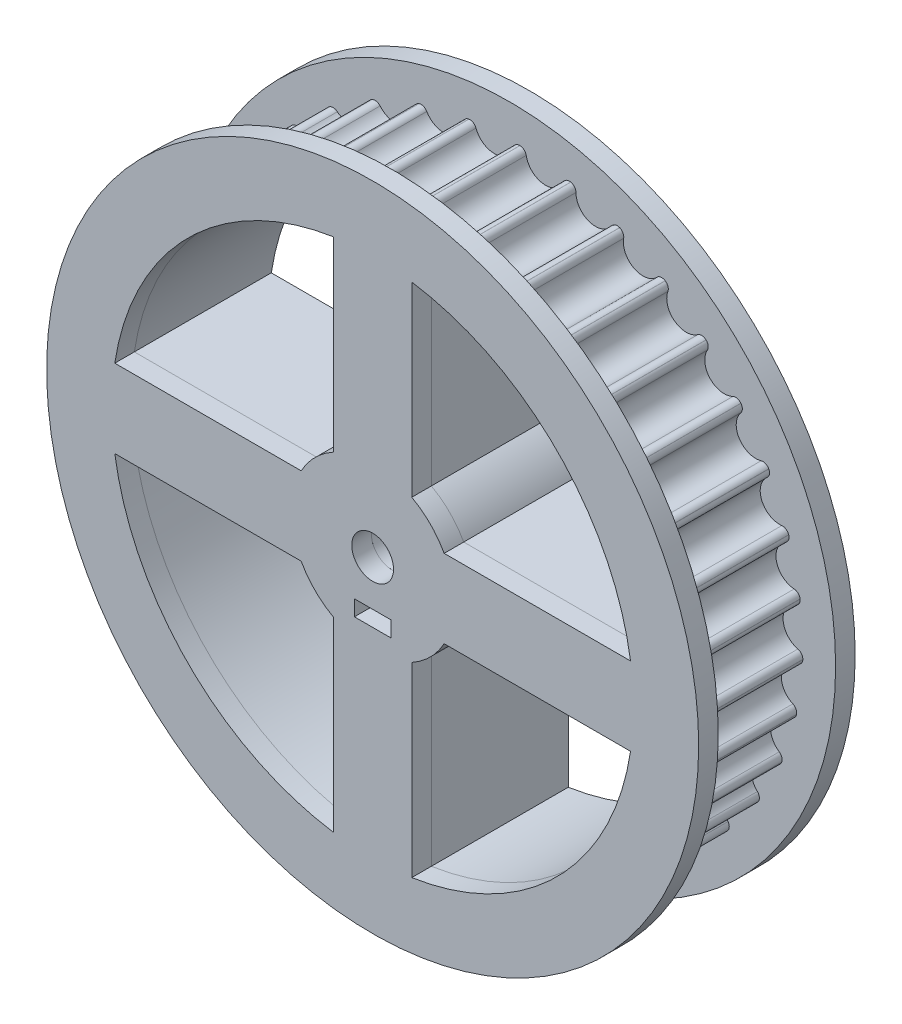
SolidWorks part; units mm, degrees
ref_plane "Front Plane" through (0, 0, 0) normal (0, 0, 1) x (1, 0, 0)
ref_plane "Top Plane" through (0, 0, 0) normal (0, 1, 0) x (1, 0, 0)
ref_plane "Right Plane" through (0, 0, 0) normal (1, 0, 0) x (0, 0, -1)
ref_plane "Plane1" through (0, 0, 18) normal (0, 0, 1) x (1, 0, 0)
sketch "Sketch1" plane through (0, 0, 0) normal (0, 0, 1) x (1, 0, 0)
  circle A0 centre (0, 0) radius 50
  circle A1 centre (0, 0) radius 45
  point P83 (0, 0)
  dimension "D1" = 100
  dimension "D2" = 90
extrude "Boss-Extrude1" add sketch "Sketch1" along normal blind 18 contours A1 region at (0, 0, 0)
sketch "Sketch3" plane through (0, 0, 0) normal (0, 0, 1) x (1, 0, 0)
  circle A0 centre (0, 0) radius 50
  dimension "D1" = 100
extrude "Boss-Extrude2" add sketch "Sketch3" against normal blind 3
sketch "Sketch10" plane through (0, 0, 18) normal (0, 0, 1) x (1, 0, 0)
  circle A0 centre (-44.6616, 5.5083) radius 3
  point P94 (0, 0)
  dimension "D1" = 6
extrude "Cut-Extrude7" cut sketch "Sketch10" against normal blind 18
fillet "Fillet1" radius 1 2 edges at (-44.1953, 8.4718, 9) (-44.9294, 2.5203, 9)
pattern_circular "CirPattern1" count 36 over 360 about axis through (0, 0, 18) along (0, 0, -1) of "Cut-Extrude7", "Fillet1" reverse direction yes
sketch "Sketch4" plane through (0, 0, 18) normal (0, 0, 1) x (1, 0, 0)
  line L0 (6, -39.5474) -> (6, -10.9659)
  line L1 (0, -11.55) -> (0, 11.55) construction
  line L2 (-6, -39.5474) -> (-6, -10.9659)
  line L3 (-39.5474, -6) -> (-10.9659, -6)
  line L4 (-39.5474, 6) -> (-10.9659, 6)
  line L5 (-6, 39.5474) -> (-6, 10.9659)
  line L6 (6, 39.5474) -> (6, 10.9659)
  line L7 (39.5474, 6) -> (10.9659, 6)
  line L8 (39.5474, -6) -> (10.9659, -6)
  arc A0 (6, -39.5474) -> (39.5474, -6) centre (0, 0) ccw
  arc A1 (-10.9659, -6) -> (-6, -10.9659) centre (0, 0) ccw
  arc A2 (-39.5474, -6) -> (-6, -39.5474) centre (0, 0) ccw
  arc A3 (10.9659, 6) -> (6, 10.9659) centre (0, 0) ccw
  arc A4 (39.5474, 6) -> (6, 39.5474) centre (0, 0) ccw
  arc A5 (-6, 39.5474) -> (-39.5474, 6) centre (0, 0) ccw
  arc A6 (-6, 10.9659) -> (-10.9659, 6) centre (0, 0) ccw
  arc A7 (6, -10.9659) -> (10.9659, -6) centre (0, 0) ccw
  circle A8 centre (0, 0) radius 3.2
  point P25 (0, 0)
  dimension "D1" = 25
  dimension "D2" = 80
  dimension "D5" = 6.4
  dimension "D3" = 6
  dimension "D4" = 4
extrude "Cut-Extrude1" cut sketch "Sketch4" against normal blind 22
sketch "Sketch5" plane through (0, 0, 18) normal (0, 0, 1) x (1, 0, 0)
  line L0 (-3, -39.6087) -> (3, -39.6087)
  line L1 (0, -11.55) -> (0, 11.55) construction
  line L2 (3, -39.6087) -> (3, -12.8861)
  line L3 (3, -12.8861) -> (-3, -12.8861)
  line L4 (-3, -39.6087) -> (-3, -12.8861)
  line L5 (-39.6087, 3) -> (-39.6087, -3)
  line L6 (-39.6087, -3) -> (-12.8861, -3)
  line L7 (-12.8861, -3) -> (-12.8861, 3)
  line L8 (-39.6087, 3) -> (-12.8861, 3)
  line L9 (3, 39.6087) -> (-3, 39.6087)
  line L10 (-3, 39.6087) -> (-3, 12.8861)
  line L11 (-3, 12.8861) -> (3, 12.8861)
  line L12 (3, 39.6087) -> (3, 12.8861)
  line L13 (39.6087, -3) -> (39.6087, 3)
  line L14 (39.6087, 3) -> (12.8861, 3)
  line L15 (12.8861, 3) -> (12.8861, -3)
  line L16 (39.6087, -3) -> (12.8861, -3)
  line L17 (-2.8, -9.314) -> (2.8, -9.314)
  line L18 (2.8, -9.314) -> (2.8, -6.914)
  line L19 (2.8, -6.914) -> (-2.8, -6.914)
  line L20 (-2.8, -9.314) -> (-2.8, -6.914)
  point P7 (0, -39.6087)
  point P8 (0, -12.8861)
  point P23 (0, 0)
  point P26 (0, -6.914)
  point P27 (0, -9.314)
  dimension "D1" = 3
  dimension "D3" = 5.6
  dimension "D4" = 2.4
  dimension "D2" = 4
extrude "Cut-Extrude2" cut sketch "Sketch5" against normal blind 25 contours L0 L2 L3 L4 | L13 L14 L15 L16 | L5 L6 L7 L8 | L9 L10 L11 L12 | L19 L20 L17 L18
sketch "Sketch6" plane through (0, 0, 0) normal (0, 1, 0) x (1, 0, 0)
  line L0 (50, 3) -> (-50, 3) construction
  line L1 (3.2, 3) -> (-3.2, 3) construction
  line L2 (0, -11.55) -> (0, 11.55) construction
  circle A0 centre (0, -4) radius 2
  circle A1 centre (0, -12) radius 2
  dimension "D3" = 4
  dimension "D1" = 7
  dimension "D2" = 15
extrude "Cut-Extrude3" cut sketch "Sketch6" along normal blind 1 and the other way blind 51
sketch "Sketch7" plane through (0, 0, 18) normal (0, 0, 1) x (1, 0, 0)
  circle A0 centre (0, 0) radius 50
extrude "Boss-Extrude3" add sketch "Sketch7" along normal blind 3 separate body
sketch "Sketch8" plane through (0, 0, 18) normal (0, 0, -1) x (-1, 0, 0)
  line L0 (12.9861, 2.9) -> (12.9861, -2.9)
  line L1 (12.9861, -2.9) -> (39.5087, -2.9)
  line L2 (39.5087, -2.9) -> (39.5087, 2.9)
  line L3 (39.5087, 2.9) -> (12.9861, 2.9)
  line L4 (2.9, -12.9861) -> (-2.9, -12.9861)
  line L5 (-2.9, -12.9861) -> (-2.9, -39.5087)
  line L6 (-2.9, -39.5087) -> (2.9, -39.5087)
  line L7 (2.9, -39.5087) -> (2.9, -12.9861)
  line L8 (-12.9861, -2.9) -> (-12.9861, 2.9)
  line L9 (-12.9861, 2.9) -> (-39.5087, 2.9)
  line L10 (-39.5087, 2.9) -> (-39.5087, -2.9)
  line L11 (-39.5087, -2.9) -> (-12.9861, -2.9)
  line L20 (-2.9, 12.9861) -> (2.9, 12.9861)
  line L21 (2.9, 12.9861) -> (2.9, 39.5087)
  line L22 (-2.9, 39.5087) -> (-2.9, 12.9861)
  line L23 (2.9, 39.5087) -> (-2.9, 39.5087)
  line L24 (-2.9, 12.9861) -> (2.9, 12.9861)
  line L25 (2.9, 12.9861) -> (2.9, 39.5087)
  line L26 (-2.9, 39.5087) -> (-2.9, 12.9861)
  line L27 (2.9, 39.5087) -> (-2.9, 39.5087)
  circle A1 centre (0, 0) radius 50
  circle A2 centre (0, 0) radius 50
  point P18 (0, 0)
  point P19 (-0.5, 0.5)
  dimension "D1" = 0.1
  dimension "D2" = 0
  dimension "D3" = 4
extrude "Boss-Extrude4" add sketch "Sketch8" along normal blind 3 separate body contours L24 L25 L27 L26 | L9 L10 L11 L8 | L5 L6 L7 L4 | L1 L2 L3 L0
sketch "Sketch9" plane through (0, 0, 18) normal (0, 0, -1) x (-1, 0, 0)
  line L20 (6, -10.9659) -> (6, -39.5474)
  line L21 (39.5474, -6) -> (10.9659, -6)
  line L22 (10.9659, 6) -> (39.5474, 6)
  line L23 (6, 39.5474) -> (6, 10.9659)
  line L24 (10.9659, 6) -> (39.5474, 6)
  line L25 (6, 39.5474) -> (6, 10.9659)
  line L26 (-10.9659, -6) -> (-39.5474, -6)
  line L27 (-6, -39.5474) -> (-6, -10.9659)
  line L28 (-6, 10.9659) -> (-6, 39.5474)
  line L29 (-39.5474, 6) -> (-10.9659, 6)
  line L44 (-2.8, -6.914) -> (-2.8, -9.314)
  line L45 (2.8, -6.914) -> (-2.8, -6.914)
  line L46 (2.8, -9.314) -> (2.8, -6.914)
  line L47 (-2.8, -9.314) -> (2.8, -9.314)
  line L48 (-2.8, -6.914) -> (-2.8, -9.314)
  line L49 (2.8, -6.914) -> (-2.8, -6.914)
  line L50 (2.8, -9.314) -> (2.8, -6.914)
  line L51 (-2.8, -9.314) -> (2.8, -9.314)
  circle A0 centre (0, 0) radius 3.2
  arc A24 (6, -39.5474) -> (39.5474, -6) centre (0, 0) ccw
  arc A25 (6, -10.9659) -> (10.9659, -6) centre (0, 0) ccw
  arc A26 (10.9659, 6) -> (6, 10.9659) centre (0, 0) ccw
  arc A27 (39.5474, 6) -> (6, 39.5474) centre (0, 0) ccw
  arc A28 (10.9659, 6) -> (6, 10.9659) centre (0, 0) ccw
  arc A29 (39.5474, 6) -> (6, 39.5474) centre (0, 0) ccw
  arc A30 (-39.5474, -6) -> (-6, -39.5474) centre (0, 0) ccw
  arc A31 (-10.9659, -6) -> (-6, -10.9659) centre (0, 0) ccw
  arc A32 (-6, 39.5474) -> (-39.5474, 6) centre (0, 0) ccw
  arc A33 (-6, 10.9659) -> (-10.9659, 6) centre (0, 0) ccw
  point P22 (0, 0)
  dimension "D3" = 6.4
  dimension "D1" = 0
  dimension "D4" = 0
  dimension "D2" = 4
extrude "Cut-Extrude4" cut sketch "Sketch9" against normal blind 3
combine bodies "Combine1" operation type add bodies to combine 117 112 113 114 115
